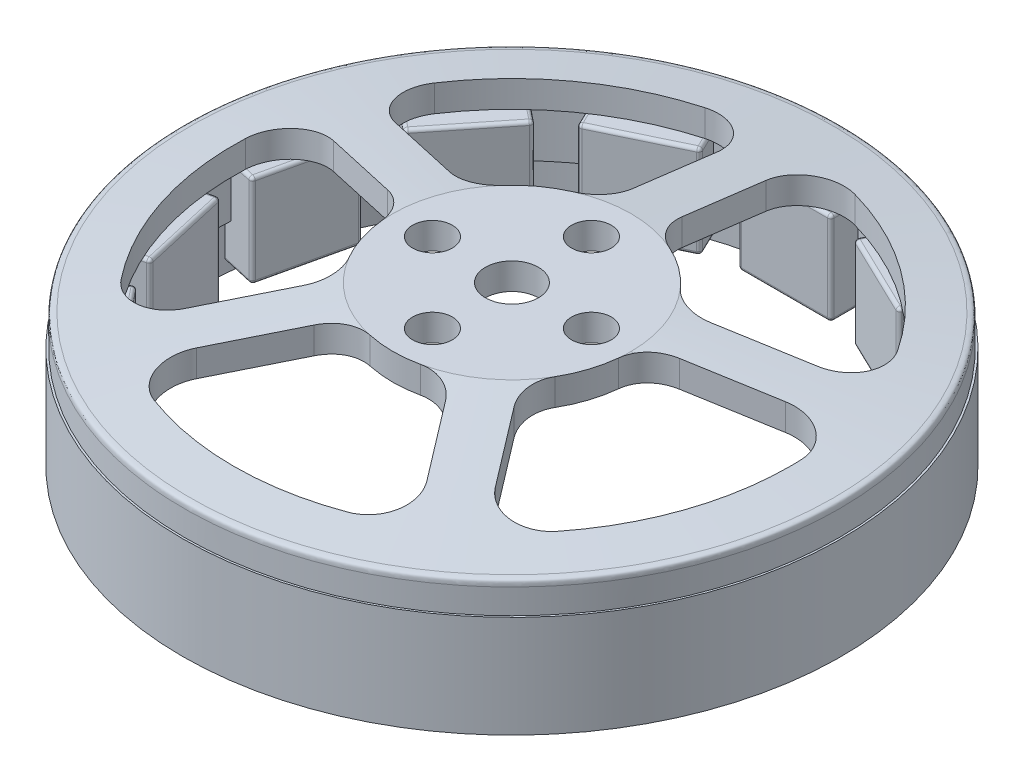
SolidWorks part; units mm, degrees
material "Литая легированная сталь"
ref_plane "Спереди" through (0, 0, 0) normal (0, 0, 1) x (1, 0, 0)
ref_plane "Сверху" through (0, 0, 0) normal (0, 1, 0) x (1, 0, 0)
ref_plane "Справа" through (0, 0, 0) normal (1, 0, 0) x (0, 0, -1)
other "Configuration Table"
sketch "Эскиз1" plane through (0, 0, 0) normal (0, 1, 0) x (1, 0, 0)
  circle A0 centre (0, 0) radius 24.875
  dimension "D1" = 49.75
extrude "Бобышка-Вытянуть1" add sketch "Эскиз1" along normal blind 12
sketch "Эскиз2" plane through (0, 0, 0) normal (0, 0, 1) x (1, 0, 0)
  line L0 (9, 12) -> (24.875, 10)
  line L1 (24.875, 12) -> (-24.875, 12) construction
  line L2 (24.875, 0) -> (24.875, 12) construction
  line L3 (24.875, 10) -> (24.875, 12)
  line L4 (24.875, 12) -> (9, 12)
  line L5 (-24.875, 0) -> (24.875, 0) construction
  line L6 (0, 0) -> (0, 12) construction
  dimension "D1" = 10
  dimension "D2" = 9
revolve "Фаска" cut sketch "Эскиз2" angle 360 about L6
shell "Оболочка1" thickness 2 removed face at (0, 0, 24.875)
sketch "Эскиз8" plane through (0, 0, 0) normal (0, 1, 0) x (1, 0, 0)
  circle A0 centre (0, 0) radius 24.725
  dimension "D1" = 49.45
extrude "Переход" cut sketch "Эскиз8" along normal through all from offset 7.7 thin thin type one direction wall 50
fillet "Скругление1" radius 0.5 1 edges at (24.725, 10.0189, 0) conic rho 0.7
sketch "Эскиз4" plane through (0, 0, 0) normal (0, 1, 0) x (1, 0, 0)
  line L0 (0, 9) -> (0, 21) construction
  line L1 (-1.85, 20.9184) -> (-1.85, 8.8078)
  line L2 (1.85, 8.8078) -> (1.85, 20.9184)
  line L3 (-1.85, 14.8631) -> (1.85, 14.8631) construction
  line L4 (8.9484, 0.9623) -> (20.4662, 4.7047)
  line L5 (19.3229, 8.2236) -> (7.805, 4.4812)
  line L6 (3.6804, -8.2131) -> (10.7988, -18.0107)
  line L7 (13.7922, -15.8359) -> (6.6738, -6.0383)
  line L8 (-6.6738, -6.0383) -> (-13.7922, -15.8359)
  line L9 (-10.7988, -18.0107) -> (-3.6804, -8.2131)
  line L10 (-7.805, 4.4812) -> (-19.3229, 8.2236)
  line L11 (-20.4662, 4.7047) -> (-8.9484, 0.9623)
  circle A0 centre (0, 0) radius 21
  circle A1 centre (0, 0) radius 9
  point P12 (0, 14.8631)
  point P32 (0, 0)
  dimension "D1" = 42
  dimension "D2" = 18
  dimension "D3" = 3.7
  dimension "D4" = 5
extrude "Прорези" cut sketch "Эскиз4" along normal through all contours A1 L1 A0 L10 | A1 L11 A0 L8 | A1 L5 A0 L2 | A1 L7 A0 L4 | A1 L9 A0 L6 region at (-8.996, 0, -12.3819) region at (8.996, 0, -12.3819) region at (-14.5558, 0, 4.7295) region at (14.5558, 0, 4.7295) region at (0, 0, 15.3048)
fillet "Скругление2" radius 3 20 edges at (10.7988, 9.4803, 18.0107) (3.6804, 10.9921, 8.2131) (-3.6804, 10.9921, 8.2131) (-10.7988, 9.4803, 18.0107) (13.7922, 9.4803, 15.8359) (20.4662, 9.4803, -4.7047) (8.9484, 10.9921, -0.9623) (6.6738, 10.9921, 6.0383) (19.3229, 9.4803, -8.2236) (7.805, 10.9921, -4.4812) (1.85, 10.9921, -8.8078) (1.85, 9.4803, -20.9184) (-1.85, 9.4803, -20.9184) (-1.85, 10.9921, -8.8078) (-7.805, 10.9921, -4.4812) (-19.3229, 9.4803, -8.2236) (-13.7922, 9.4803, 15.8359) (-20.4662, 9.4803, -4.7047) (-6.6738, 10.9921, 6.0383) (-8.9484, 10.9921, -0.9623)
sketch "Эскиз5" plane through (0, 0, 0) normal (0, 1, 0) x (1, 0, 0)
  line L0 (0, 23.475) -> (0, 24.875) construction
  circle A0 centre (0, 0) radius 23.475
  circle A2 centre (0, 0) radius 24.875 construction
  dimension "D1" = 1.4
extrude "Утоншение под магниты" cut sketch "Эскиз5" along normal blind 3.8
sketch "Эскиз6" plane through (0, 0, 0) normal (0, 1, 0) x (1, 0, 0)
  line L0 (0, 0) -> (0, -22.025) construction
  line L1 (0, -23.475) -> (0, -24.875) construction
  line L2 (3.5, -20.575) -> (-3.5, -20.575)
  line L3 (3.5, -20.575) -> (3.5, -23.475)
  line L4 (3.5, -23.475) -> (-3.5, -23.475)
  line L5 (-3.5, -20.575) -> (-3.5, -23.475)
  line L6 (0, -23.475) -> (0, -20.575) construction
  line L7 (3.5, -22.025) -> (-3.5, -22.025) construction
  circle A0 centre (0, 0) radius 23.475 construction
  circle A1 centre (0, 0) radius 24.875 construction
  dimension "D1" = 4.3
  dimension "D2" = 7
extrude "Магнит" add sketch "Эскиз6" along normal blind 7 from offset 0.8
fillet "Скругление3" radius 0.25 8 edges at (3.5, 4.3, 20.575) (0, 7.8, 20.575) (-3.5, 4.3, 20.575) (0, 0.8, 20.575) (-3.5, 0.8, 21.8938) (-3.5, 7.8, 21.5903) (3.5, 7.8, 21.5903) (3.5, 0.8, 21.8938)
pattern_circular "Круговой массив1" count 14 over 360 about axis through (0, 12, 0) along (0, -1, 0) of "Скругление3", "Магнит" reverse direction yes
sketch "Эскиз7" plane through (0, 0, 0) normal (0, 1, 0) x (1, 0, 0)
  circle A0 centre (0, 0) radius 6 construction
  circle A1 centre (0, 6) radius 1.5
  circle A2 centre (6, 0) radius 1.5
  circle A3 centre (0, -6) radius 1.5
  circle A4 centre (-6, 0) radius 1.5
  circle A5 centre (0, 0) radius 2
  dimension "D1" = 3
  dimension "D2" = 12
  dimension "D3" = 4
extrude "Отверстия" cut sketch "Эскиз7" along normal through all
